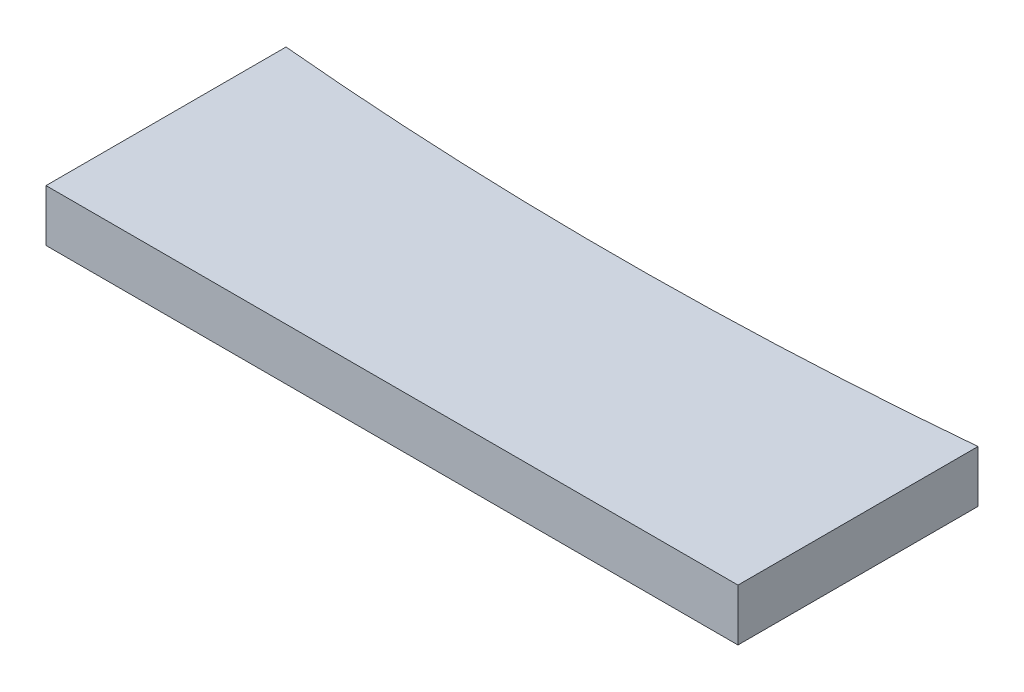
SolidWorks part; units mm, degrees
material "PTFE (general)"
ref_plane "Front Plane" through (0, 0, 0) normal (0, 0, 1) x (1, 0, 0)
ref_plane "Top Plane" through (0, 0, 0) normal (0, 1, 0) x (1, 0, 0)
ref_plane "Right Plane" through (0, 0, 0) normal (1, 0, 0) x (0, 0, -1)
sketch "Sketch1" plane through (0, 0, 0) normal (0, 1, 0) x (1, 0, 0)
  line L0 (-5.08, -55.3298) -> (-5.08, -58.5174)
  line L1 (5.08, -55.3298) -> (5.08, -58.5174)
  line L2 (-5.08, -58.8541) -> (5.08, -58.8541)
  line L3 (-5.08, -58.5174) -> (-5.08, -58.8541)
  line L4 (5.08, -58.5174) -> (5.08, -58.8541)
  line L5 (12.7, -54.0916) -> (12.7, -58.8541) construction
  line L6 (12.7, -58.8541) -> (5.08, -58.8541) construction
  line L7 (0, -55.5625) -> (0, -60.0923) construction
  circle A0 centre (0, 0) radius 55.5625
  circle A1 centre (0, 0) radius 58.7375
  dimension "D1" = 111.125
  dimension "D3" = 5.08
  dimension "D4" = 5.08
  dimension "D5" = 12.7
  dimension "D6" = 4.7625
  dimension "D2" = 3.175
extrude "Boss-Extrude1" add sketch "Sketch1" along normal blind 0.762 contours L0 A1 L1 A0 | A1 L3 L2 | A1 L2 L4 region at (0, 0, 57.0745) region at (0, 0, 58.7478)
equation "\"Middle Coupler Inner Daimeter\"= 3.875in"
equation "\"Middle Coupler  Wall Thickness\" = 0.25in"
equation "\"Middle Coupler Bottom Thickness\"= 0.2in"
equation "\"Bearing Rail Offset\"= 0.45in"
equation "\"3-56 UNF Tap\"= 0.089in"
equation "\"3-56 UNF Clearance\"= 0.104in"
equation "\"Ball Bearing Distance\"= 0.03in"
equation "\"TCA Outer Diameter\" = 6in"
equation "\"D1@Sketch1\"=\"Middle Coupler Inner Daimeter\"+0.5"
equation "\"D2@Sketch1\"=1/8"
equation "\"Interstage Aeroframe Wall Thickness\" = 0.072in"
equation "\"Compression Spring OD\"= 0.42in"
equation "\"10-24 Tap\"= 0.157in"
equation "\"10-24 Clearance\"= 0.196in"
equation "\"Lower Stage Fuselage Wall Thickness\" = 0.25in"
equation "\"6-32 Tap\" = 0.107in"
equation "\"1/4-20 Tap\" = 0.201in"
equation "\"3-48 Tap\"= 0.079in"
equation "\"3-48 Clearance\" = 0.104in"
equation "\"6-32 Clearance\" = 0.144"
equation "\"12-24 Tap\" = 0.177in"
equation "\"D6@Sketch1\"=3/16"
